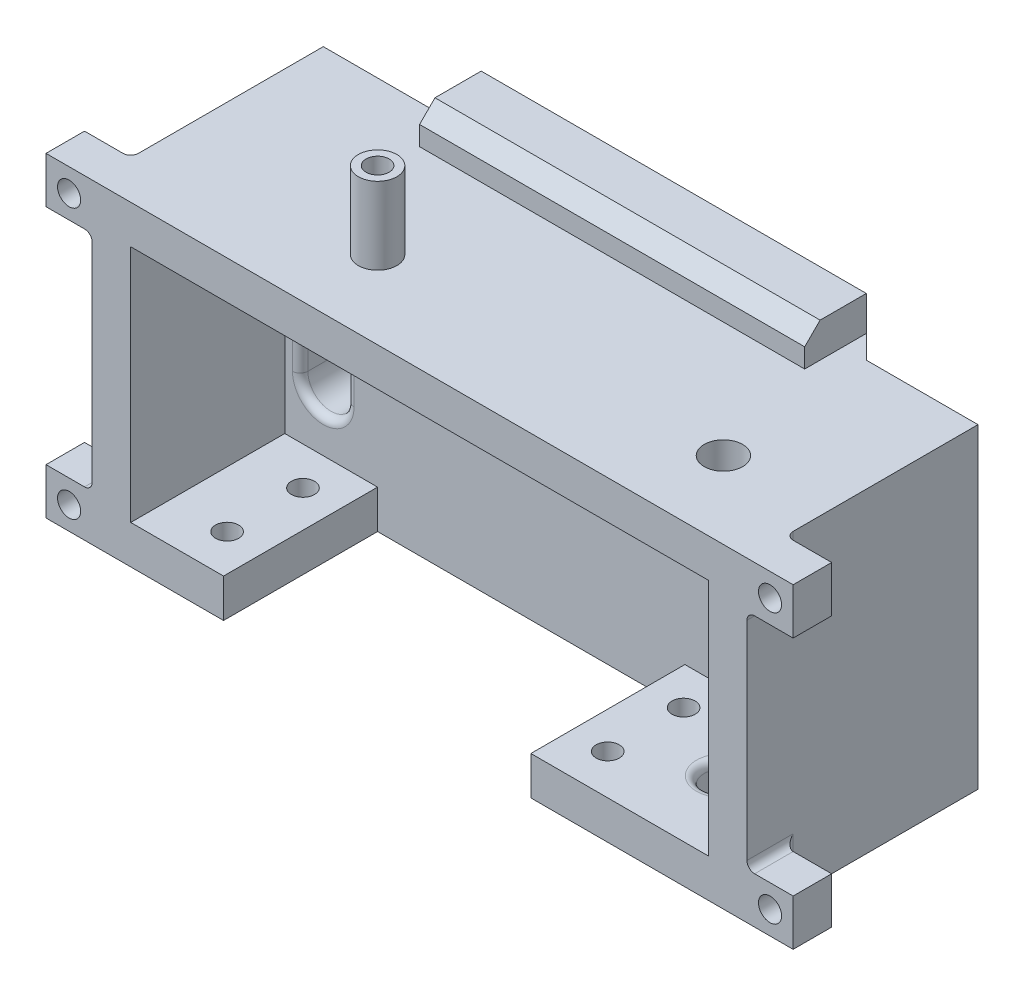
SolidWorks part; units mm, degrees
ref_plane "Front Plane" through (0, 0, 0) normal (0, 0, 1) x (1, 0, 0)
ref_plane "Top Plane" through (0, 0, 0) normal (0, 1, 0) x (1, 0, 0)
ref_plane "Right Plane" through (0, 0, 0) normal (1, 0, 0) x (0, 0, -1)
sketch "Sketch1" plane through (0, 0, 0) normal (0, 0, 1) x (1, 0, 0)
  line L1 (0, 0) -> (17.05, 0)
  line L2 (0, 0) -> (0, 41)
  line L3 (0, 41) -> (5, 41)
  line L4 (85, 0) -> (85, 41)
  line L8 (5, 41) -> (5, 5)
  line L9 (5, 5) -> (17.05, 5)
  line L10 (80, 5) -> (80, 41)
  line L11 (80, 41) -> (85, 41)
  line L12 (17.05, 5) -> (17.05, 0)
  line L13 (56.95, 5) -> (56.95, 0)
  line L14 (56.95, 5) -> (70.95, 5)
  line L15 (56.95, 0) -> (70.95, 0)
  line L16 (70.95, 5) -> (70.95, 0)
  line L17 (75.95, 5) -> (75.95, 0)
  line L18 (75.95, 5) -> (80, 5)
  line L19 (75.95, 0) -> (85, 0)
  line L20 (73.45, 8.3915) -> (73.45, -2.2005) construction
  point P17 (75.95, 2.5)
  dimension "D1" = 85
  dimension "D2" = 41
  dimension "D3" = 5
  dimension "D4" = 5
  dimension "D5" = 5
  dimension "D6" = 12.05
  dimension "D7" = 39.9
  dimension "D8" = 14
  dimension "D9" = 5
  dimension "D10" = 2.5
sketch "Sketch3" plane through (0, 0, 0) normal (0, 0, 1) x (1, 0, 0)
  line L0 (5, 36) -> (5, 5)
  line L1 (0, 41) -> (5, 41)
  line L2 (0, 41) -> (0, 0)
  line L3 (0, 0) -> (17.05, 0)
  line L4 (85, 41) -> (85, 0)
  line L5 (5, 5) -> (17.05, 5)
  line L6 (17.05, 5) -> (17.05, 0)
  line L7 (56.95, 0) -> (56.95, 5)
  line L8 (56.95, 5) -> (80, 5)
  line L9 (80, 5) -> (80, 36)
  line L10 (80, 41) -> (85, 41)
  line L11 (56.95, 0) -> (85, 0)
  line L12 (5, 41) -> (80, 41)
  line L13 (5, 36) -> (80, 36)
  dimension "D1" = 5
extrude "Boss-Extrude3" add sketch "Sketch3" along normal blind 20
sketch "Sketch4" plane through (0, 0, 0) normal (0, 0, -1) x (-1, 0, 0)
  line L1 (-85, 41) -> (0, 41)
  line L2 (-85, 41) -> (-85, 0)
  line L3 (-85, 0) -> (0, 0)
  line L4 (0, 41) -> (0, 0)
extrude "Boss-Extrude4" add sketch "Sketch4" along normal blind 10
sketch "Sketch5" plane through (0, 5, 0) normal (0, 1, 0) x (1, 0, 0)
  line L4 (56.95, -20) -> (56.95, 0) construction
  line L5 (80, -20) -> (56.95, -20) construction
  circle A0 centre (71.95, -10) radius 2.5
  dimension "D1" = 5
  dimension "D2" = 15
  dimension "D3" = 10
extrude "Cut-Extrude1" cut sketch "Sketch5" against normal blind 5
sketch "Sketch6" plane through (0, 36, 0) normal (0, -1, 0) x (1, 0, 0)
  line L0 (56.95, 20) -> (56.95, 0) construction
  line L1 (56.95, 20) -> (85, 20) construction
  circle A0 centre (71.95, 10) radius 2.5
  dimension "D1" = 5
  dimension "D2" = 15
  dimension "D3" = 10
extrude "Cut-Extrude2" cut sketch "Sketch6" against normal blind 5
fillet "Fillet2" radius 1 2 edges at (71.95, 36, 7.5) (71.95, 5, 12.5)
sketch "Sketch7" plane through (0, 5, 0) normal (0, 1, 0) x (1, 0, 0)
  line L0 (17.05, -20) -> (17.05, 0) construction
  line L1 (56.95, 0) -> (17.05, 0) construction
  circle A0 centre (12.29, -4.93) radius 1.5
  circle A1 centre (12.29, -14.78) radius 1.5
  dimension "D1" = 3
  dimension "D2" = 4.76
  dimension "D3" = 4.93
  dimension "D4" = 9.85
  dimension "D5" = 3
  dimension "D6" = 4.76
extrude "Cut-Extrude3" cut sketch "Sketch7" against normal blind 5
ref_plane "Plane1" through (37, 0, 0) normal (1, 0, 0) x (0, 0, -1)
mirror "Mirror1" about plane through (37, 0, 0) normal (1, 0, 0) of "Cut-Extrude3"
sketch "Sketch8" plane through (0, 0, 0) normal (0, 0, 1) x (1, 0, 0)
  line L0 (10, 27.5) -> (10, 12.5) construction
  line L1 (13, 27.5) -> (13, 12.5)
  line L2 (7, 27.5) -> (7, 12.5)
  line L3 (17.05, 5) -> (5, 5) construction
  line L4 (5, 5) -> (5, 36) construction
  arc A0 (13, 27.5) -> (7, 27.5) centre (10, 27.5) ccw
  arc A1 (7, 12.5) -> (13, 12.5) centre (10, 12.5) ccw
  point P2 (10, 20)
  dimension "D1" = 3
  dimension "D2" = 15
  dimension "D3" = 15
  dimension "D4" = 5
extrude "Cut-Extrude4" cut sketch "Sketch8" against normal blind 10
fillet "Fillet3" radius 1 4 edges at (10, 30.5, 0) (13, 20, 0) (10, 9.5, 0) (7, 20, 0)
sketch "Sketch9" plane through (0, 0, -10) normal (0, 0, -1) x (-1, 0, 0)
  line L0 (-99.4869, 20.5) -> (13.5233, 20.5) construction
  line L1 (-42.5, 50.5202) -> (-42.5, -6.8796) construction
  line L2 (-59.2, 24.3) -> (-48.0118, 24.5)
  line L3 (-67.5, 45.5) -> (-17.5, 45.5)
  line L4 (-67.5, 45.5) -> (-67.5, -4.5)
  line L5 (-67.5, -4.5) -> (-17.5, -4.5)
  line L6 (-17.5, 45.5) -> (-17.5, -4.5)
  line L7 (-46.5, 26.0118) -> (-46.3, 37.2)
  line L8 (-25.8, 24.3) -> (-36.9882, 24.5)
  line L9 (-38.5, 26.0118) -> (-38.7, 37.2)
  line L10 (-59.2, 16.7) -> (-48.0118, 16.5)
  line L11 (-46.5, 14.9882) -> (-46.3, 3.8)
  line L12 (-38.5, 14.9882) -> (-38.7, 3.8)
  line L13 (-25.8, 16.7) -> (-36.9882, 16.5)
  arc A0 (-59.2, 24.3) -> (-59.2, 16.7) centre (-59.2, 20.5) ccw
  arc A1 (-48.0118, 24.5) -> (-46.5, 26.0118) centre (-47.9381, 25.9381) ccw
  arc A2 (-38.7, 37.2) -> (-46.3, 37.2) centre (-42.5, 37.2) ccw
  arc A3 (-25.8, 24.3) -> (-25.8, 16.7) centre (-25.8, 20.5) cw
  arc A4 (-36.9882, 24.5) -> (-38.5, 26.0118) centre (-37.0619, 25.9381) cw
  arc A5 (-38.7, 3.8) -> (-46.3, 3.8) centre (-42.5, 3.8) cw
  arc A6 (-48.0118, 16.5) -> (-46.5, 14.9882) centre (-47.9381, 15.0619) cw
  arc A7 (-36.9882, 16.5) -> (-38.5, 14.9882) centre (-37.0619, 15.0619) ccw
  dimension "D5" = 7.6
  dimension "D6" = 7.6
  dimension "D11" = 1.44
  dimension "D1" = 50
  dimension "D2" = 50
  dimension "D3" = 25
  dimension "D4" = 25
  dimension "D7" = 11.19
  dimension "D10" = 11.19
  dimension "D12" = 4
  dimension "D13" = 4
sketch "Sketch10" plane through (0, 0, -10) normal (0, 0, -1) x (-1, 0, 0)
  line L1 (-67.5, 45.5) -> (-17.5, 45.5)
  line L2 (-67.5, 45.5) -> (-67.5, -4.5)
  line L3 (-67.5, -4.5) -> (-17.5, -4.5)
  line L4 (-17.5, 45.5) -> (-17.5, -4.5)
extrude "Boss-Extrude7" add sketch "Sketch10" against normal blind 5
extrude "Boss-Extrude8" add sketch "Sketch9" along normal blind 5
sketch "Sketch11" plane through (0, 0, -10) normal (0, 0, -1) x (-1, 0, 0)
  line L0 (-65.7628, 20.5) -> (-18.549, 20.5) construction
  line L1 (-42.5, 43.9004) -> (-42.5, -3.5887) construction
  circle A0 centre (-59, 20.5) radius 0.75
  circle A1 centre (-26, 20.5) radius 0.75
  dimension "D1" = 1.5
  dimension "D2" = 16.5
extrude "Cut-Extrude5" cut sketch "Sketch11" against normal blind 5
chamfer "Chamfer1" distance 2 angle 45 6 edges at (42.5, -4.5, -5) (17.5, 20.5, -15) (42.5, -4.5, -15) (67.5, 20.5, -15) (42.5, 45.5, -15) (42.5, 45.5, -5)
sketch "Sketch12" plane through (0, 41, 0) normal (0, 1, 0) x (1, 0, 0)
  line L1 (80.3536, -10) -> (-4.7138, -10) construction
  line L2 (0, -20) -> (0, 10) construction
  circle A6 centre (26.9, -10) radius 2.5
  dimension "D1" = 5
  dimension "D2" = 26.9
extrude "Boss-Extrude9" [suppressed] add sketch "Sketch12" along normal blind 10
sketch "Sketch13" [suppressed] plane through (0, 41, 0) normal (0, 1, 0) x (1, 0, 0)
  circle A0 centre (26.9, -10) radius 5
  dimension "D1" = 10
extrude "Boss-Extrude10" [suppressed] add sketch "Sketch13" along normal blind 5
fillet "Fillet4" [suppressed] radius 2
sketch "Sketch14" [suppressed] plane through (0, 51, 0) normal (0, 1, 0) x (1, 0, 0)
  circle A0 centre (26.9, -10) radius 1.5
  dimension "D1" = 3
extrude "Cut-Extrude6" [suppressed] cut sketch "Sketch14" against normal blind 5
chamfer "Chamfer2" distance 3 angle 45 2 edges at (17.5, 20.5, -10) (67.5, 20.5, -10)
sketch "Sketch15" plane through (0, 0, 20) normal (0, 0, 1) x (1, 0, 0)
  line L0 (0, 41) -> (0, 0) construction
  line L1 (-6, 41) -> (0, 41)
  line L2 (-6, 41) -> (-6, 35)
  line L3 (-6, 35) -> (0, 35)
  line L4 (0, 41) -> (0, 35)
  line L5 (85, 41) -> (0, 41) construction
  circle A0 centre (-3, 38) radius 1.5
  dimension "D3" = 3
  dimension "D4" = 3
  dimension "D5" = 3
  dimension "D1" = 6
  dimension "D2" = 6
extrude "Boss-Extrude11" add sketch "Sketch15" against normal blind 5
pattern_linear "LPattern1" count 2 spacing 35 along (0, -1, 0) count 2 spacing 91 along (1, 0, 0) of "Boss-Extrude11"
fillet "Fillet5" radius 1 8 edges at (0, 6, 17.5) (0, 3, 15) (0, 35, 17.5) (0, 38, 15) (85, 35, 17.5) (85, 38, 15) (85, 6, 17.5) (85, 3, 15)
sketch "Sketch16" plane through (0, 41, 0) normal (0, 1, 0) x (1, 0, 0)
  line L0 (74.4455, -9.85) -> (3.7007, -9.85) construction
  line L1 (91, -20) -> (-6, -20) construction
  circle A0 centre (71.95, -10) radius 2.5 construction
  circle A1 centre (26.9002, -9.85) radius 2.5
  point P9 (0, 0)
  dimension "D1" = 5
  dimension "D2" = 45.05
  dimension "D3" = 10.15
extrude "Boss-Extrude12" add sketch "Sketch16" along normal blind 10
sketch "Sketch17" plane through (0, 51, 0) normal (0, 1, 0) x (1, 0, 0)
  circle A0 centre (26.9002, -9.85) radius 1.5
  dimension "D1" = 3
extrude "Cut-Extrude8" cut sketch "Sketch17" against normal blind 5
